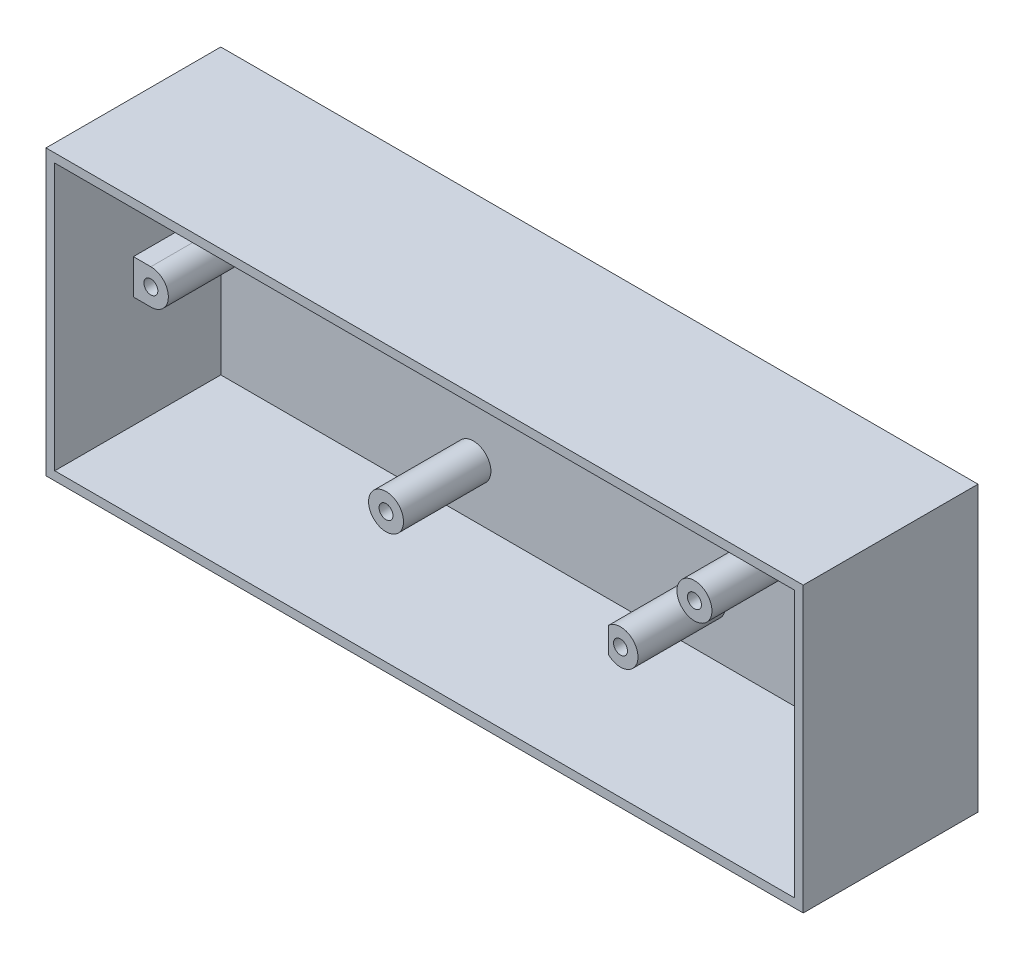
SolidWorks part; units mm, degrees
ref_plane "Front Plane" through (0, 0, 0) normal (0, 0, 1) x (1, 0, 0)
ref_plane "Top Plane" through (0, 0, 0) normal (0, 1, 0) x (1, 0, 0)
ref_plane "Right Plane" through (0, 0, 0) normal (1, 0, 0) x (0, 0, -1)
sketch "Sketch1" plane through (0, 0, 0) normal (0, 0, 1) x (1, 0, 0)
  line L1 (-70.1278, 62.2356) -> (103.1722, 62.2356)
  line L2 (-70.1278, 62.2356) -> (-70.1278, -2.7644)
  line L3 (-70.1278, -2.7644) -> (103.1722, -2.7644)
  line L4 (103.1722, 62.2356) -> (103.1722, -2.7644)
  dimension "D1" = 173.3
  dimension "D2" = 65
extrude "Boss-Extrude1" add sketch "Sketch1" along normal blind 60
shell "Shell1" thickness 2
sketch "Sketch3" plane through (0, 0, 60) normal (0, 0, 1) x (1, 0, 0)
  line L1 (-106.5133, 69.14) -> (112.8577, 69.14)
  line L2 (-106.5133, 69.14) -> (-106.5133, -25.4988)
  line L3 (-106.5133, -25.4988) -> (112.8577, -25.4988)
  line L4 (112.8577, 69.14) -> (112.8577, -25.4988)
extrude "Cut-Extrude3" cut sketch "Sketch3" against normal blind 20
sketch "Sketch5" plane through (0, 0, 2) normal (0, 0, 1) x (1, 0, 0)
  line L0 (-68.1278, 60.2356) -> (-60.1278, 60.2356)
  line L1 (101.1722, 60.2356) -> (-68.1278, 60.2356) construction
  line L2 (101.1722, 60.2356) -> (93.1722, 60.2356)
  line L4 (-60.1278, 60.2356) -> (-60.1278, 56.2356)
  line L5 (101.1722, 60.2356) -> (-68.1278, 60.2356) construction
  line L6 (-64.1278, 52.2356) -> (-68.1278, 52.2356)
  line L7 (-68.1278, 52.2356) -> (-68.1278, 60.2356)
  line L8 (-68.1278, 60.2356) -> (-68.1278, -0.7644) construction
  line L9 (101.1722, 60.2356) -> (101.1722, 52.2356)
  line L10 (-31.2278, 60.2356) -> (-15.7278, 60.2356)
  line L11 (-31.2278, 60.2356) -> (-31.2278, 56.2356)
  line L12 (-27.2278, 52.2356) -> (-19.7278, 52.2356)
  line L13 (-15.7278, 60.2356) -> (-15.7278, 56.2356)
  line L14 (101.1722, 52.2356) -> (97.1722, 52.2356)
  line L15 (93.1722, 60.2356) -> (93.1722, 56.2356)
  line L16 (56.2722, 60.2356) -> (64.2722, 60.2356)
  line L17 (56.2722, 60.2356) -> (56.2722, 56.2356)
  line L19 (64.2722, 60.2356) -> (64.2722, 56.2356)
  line L20 (101.1722, -0.7644) -> (101.1722, 60.2356) construction
  line L21 (-68.1278, 60.2356) -> (-68.1278, -0.7644) construction
  line L22 (-68.1278, 32.6856) -> (-64.1278, 32.6856)
  line L23 (-68.1278, 32.6856) -> (-68.1278, 24.6856)
  line L24 (-68.1278, 24.6856) -> (-64.1278, 24.6856)
  line L25 (-68.1278, -0.7644) -> (101.1722, -0.7644) construction
  line L26 (40.5522, 13.9122) -> (40.5522, 8.1991)
  line L27 (-68.1278, -0.7644) -> (101.1722, -0.7644) construction
  arc A0 (-64.1278, 52.2356) -> (-60.1278, 56.2356) centre (-64.1278, 56.2356) ccw
  arc A1 (-27.2278, 52.2356) -> (-31.2278, 56.2356) centre (-27.2278, 56.2356) cw
  arc A2 (-15.7278, 56.2356) -> (-19.7278, 52.2356) centre (-19.7278, 56.2356) cw
  arc A3 (97.1722, 52.2356) -> (93.1722, 56.2356) centre (97.1722, 56.2356) cw
  arc A4 (56.2722, 56.2356) -> (64.2722, 56.2356) centre (60.2722, 56.2356) ccw
  circle A5 centre (-10.3078, 11.0556) radius 4
  arc A6 (40.5522, 8.1991) -> (40.5522, 13.9122) centre (43.3522, 11.0556) ccw
  arc A7 (-64.1278, 24.6856) -> (-64.1278, 32.6856) centre (-64.1278, 28.6856) ccw
  circle A8 centre (60.2722, 28.6856) radius 4
  point P16 (-31.2278, 52.2356)
  point P19 (-15.7278, 52.2356)
  point P27 (93.1722, 52.2356)
  dimension "D1" = 8
  dimension "D7" = 4
  dimension "D8" = 4
  dimension "D11" = 4
  dimension "D16" = 4
  dimension "D19" = 8
  dimension "D3" = 4
  dimension "D13" = 4
  dimension "D26" = 128.4
  dimension "D2" = 8
  dimension "D4" = 15.5
  dimension "D5" = 36.9
  dimension "D6" = 8
  dimension "D9" = 8
  dimension "D10" = 8
  dimension "D12" = 8
  dimension "D14" = 4
  dimension "D15" = 36.9
  dimension "D17" = 4
  dimension "D18" = 8
  dimension "D20" = 27.55
  dimension "D21" = 4
  dimension "D22" = 11.82
  dimension "D23" = 57.82
  dimension "D24" = 2.8
  dimension "D25" = 111.48
  dimension "D27" = 29.45
extrude "Boss-Extrude2" add sketch "Sketch5" along normal blind 20
sketch "Sketch6" plane through (0, 0, 22) normal (0, 0, 1) x (1, 0, 0)
  line L0 (-19.7278, 53.1466) -> (-19.7278, 57.6221) construction
  line L1 (-32.4055, 56.2356) -> (-24.2231, 56.2356) construction
  circle A0 centre (-64.1278, 56.2356) radius 1.6
  circle A1 centre (-27.2278, 56.2356) radius 1.6
  circle A2 centre (-19.7278, 56.2356) radius 1.6
  circle A3 centre (60.2722, 56.2356) radius 1.6
  circle A4 centre (97.1722, 56.2356) radius 1.6
  circle A5 centre (-64.1278, 28.6856) radius 1.6
  circle A6 centre (-10.3078, 11.0556) radius 1.6
  circle A7 centre (43.3522, 11.0556) radius 1.6
  circle A8 centre (60.2722, 28.6856) radius 1.6
  dimension "D1" = 3.2
extrude "Cut-Extrude5" cut sketch "Sketch6" against normal blind 4
